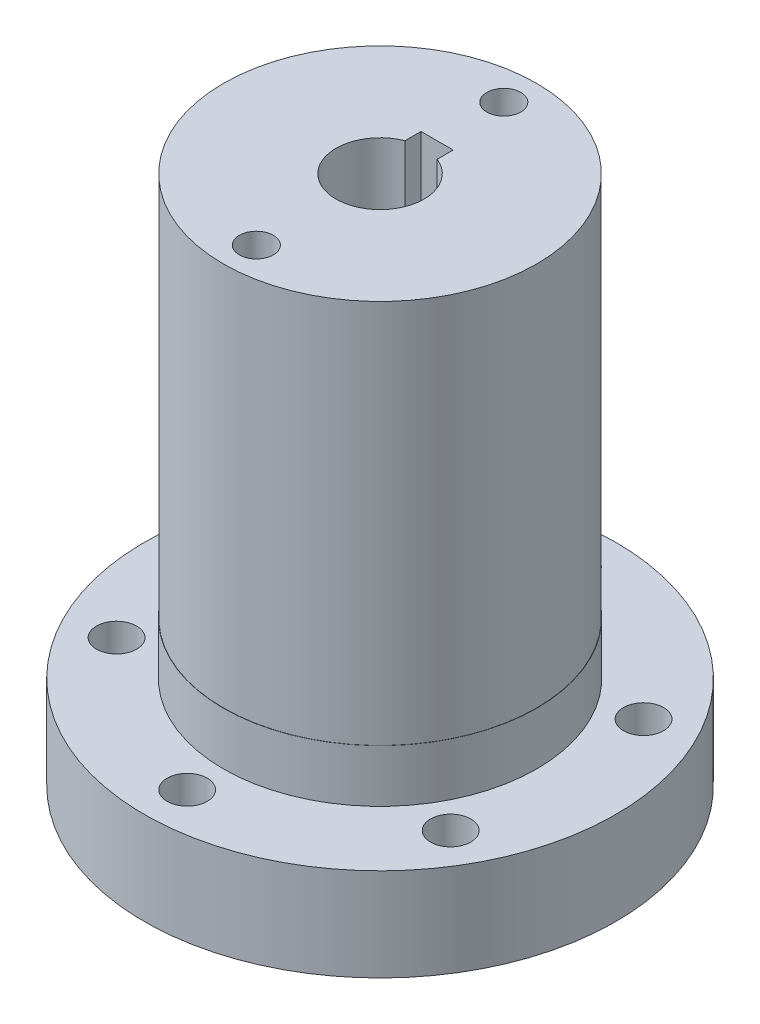
SolidWorks part; units mm, degrees
ref_plane "Front Plane" through (0, 0, 0) normal (0, 0, 1) x (1, 0, 0)
ref_plane "Top Plane" through (0, 0, 0) normal (0, 1, 0) x (1, 0, 0)
ref_plane "Right Plane" through (0, 0, 0) normal (1, 0, 0) x (0, 0, -1)
sketch "Sketch1" plane through (0, 0, 0) normal (0, 1, 0) x (1, 0, 0)
  circle A0 centre (0, 0) radius 25.34
extrude "Boss-Extrude1" add sketch "Sketch1" along normal blind 8.5
sketch "Sketch2" plane through (0, 8.5, 0) normal (0, 1, 0) x (1, 0, 0)
  circle A0 centre (0, 0) radius 25.3
extrude "Boss-Extrude2" add sketch "Sketch2" along normal blind 57.15
sketch "Sketch7" plane through (0, 65.65, 0) normal (0, 1, 0) x (1, 0, 0)
  circle A0 centre (0, 0) radius 25.3
extrude "Boss-Extrude4" add sketch "Sketch7" along normal blind 15
sketch "Sketch5" plane through (0, 0, 0) normal (0, -1, 0) x (1, 0, 0)
  line L1 (-2.575, 9.15) -> (2.575, 9.15)
  line L2 (-2.575, 9.15) -> (-2.575, 4)
  line L3 (-2.575, 4) -> (2.575, 4)
  line L4 (2.575, 9.15) -> (2.575, 4)
  circle A0 centre (0, 0) radius 7.25
  dimension "D1" = 5.15
  dimension "D2" = 5.15
  dimension "D3" = 9.15
  dimension "D4" = 2.575
extrude "Cut-Extrude3" cut sketch "Sketch5" against normal blind 115 contours L2 A0 L4 L3 | L4 A0 L2 L3 | A0 L4 L1 L2 region at (0, 0, 8.1175) region at (0, 0, 5.5505) region at (0, 0, -0.5929)
sketch "Sketch6" plane through (0, 0, 0) normal (0, -1, 0) x (1, 0, 0)
  circle A0 centre (0, 0) radius 38.1
extrude "Boss-Extrude3" add sketch "Sketch6" along normal blind 15
sketch "Sketch9" plane through (0, 0, 0) normal (0, 1, 0) x (1, 0, 0)
  line L1 (0, 31.1769) -> (-27, 15.5885)
  line L2 (-27, 15.5885) -> (-27, -15.5885)
  line L3 (-27, -15.5885) -> (0, -31.1769)
  line L4 (0, -31.1769) -> (27, -15.5885)
  line L5 (27, -15.5885) -> (27, 15.5885)
  line L6 (27, 15.5885) -> (0, 31.1769)
  circle A0 centre (0, 0) radius 27 construction
  circle A1 centre (0, 31.1769) radius 3.25
  circle A2 centre (-27, 15.5885) radius 3.25
  circle A3 centre (-27, -15.5885) radius 3.25
  circle A4 centre (0, -31.1769) radius 3.25
  circle A5 centre (27, -15.5885) radius 3.25
  circle A6 centre (27, 15.5885) radius 3.25
extrude "Cut-Extrude4" cut sketch "Sketch9" against normal blind 20 contours L1 A2 L2 | L2 A2 L1 | L6 A1 L1 | L1 A1 L6 | L5 A6 L6 | L6 A6 L5 | L4 A5 L5 | L5 A5 L4 | L3 A4 L4 | L4 A4 L3 | L2 A3 L3 | L3 A3 L2 region at (0, 0, -29.3851) region at (0, 0, -32.0728) region at (-25.4482, 0, -14.6925) region at (-27.7759, 0, -16.0364) region at (27.7759, 0, -16.0364) region at (25.4482, 0, -14.6925) region at (-25.4482, 0, 14.6925) region at (-27.7759, 0, 16.0364) region at (27.7759, 0, 16.0364) region at (25.4482, 0, 14.6925) region at (0, 0, 29.3851) region at (0, 0, 32.0728)
sketch "Sketch10" plane through (0, 80.65, 0) normal (0, 1, 0) x (1, 0, 0)
  circle A0 centre (0, 20) radius 2.75
  circle A1 centre (0, -20) radius 2.75
  arc A2 (2.575, -6.7773) -> (-2.575, -6.7773) centre (0, 0) ccw construction
  dimension "D1" = 20
  dimension "D2" = 20
extrude "Cut-Extrude6" cut sketch "Sketch10" against normal blind 129
sketch "Sketch11" plane through (0, 80.65, 0) normal (0, 1, 0) x (1, 0, 0)
  line L1 (-2.575, -9.15) -> (2.575, -9.15)
  line L3 (0, -7.12) -> (0, -9.15)
  circle A0 centre (0, 0) radius 7.12
  arc M3 (-2.575, -6.7773) -> (2.575, -6.7773) centre (0, 0) cw
  line M4 (2.575, -6.7773) -> (2.575, -9.15)
  line M5 (2.575, -9.15) -> (-2.575, -9.15)
  line M6 (-2.575, -9.15) -> (-2.575, -6.7773)
  dimension "D1" = 14.24
extrude "Boss-Extrude5" add sketch "Sketch11" against normal blind 93 contours A0 M3 | A0 M6 M5 M4 region at (0, 80.65, 0) region at (-2.3561, 80.65, 7.9637)
sketch "Sketch12" plane through (0, 80.65, 0) normal (0, 1, 0) x (1, 0, 0)
  circle A0 centre (0, 0) radius 25.3
extrude "Cut-Extrude8" cut sketch "Sketch12" against normal blind 10
sketch "Sketch13" plane through (0, 70.65, 0) normal (0, 1, 0) x (1, 0, 0)
  line L0 (0, 7.12) -> (0, 9.22)
  line L1 (0, 9.22) -> (2.6, 9.22)
  line L2 (0, 9.22) -> (-2.6, 9.22)
  line L3 (-2.6, 9.22) -> (-2.6, 6.6283)
  line L4 (2.6, 9.22) -> (2.6, 6.6283)
  circle A0 centre (0, 0) radius 7.12
extrude "Cut-Extrude9" cut sketch "Sketch13" against normal blind 30 contours A0 | A0 L0 L2 L3 | A0 L4 L1 L0 region at (-1.3468, 70.65, -8.0845) region at (1.3468, 70.65, -8.0845) region at (0, 70.65, 0)
